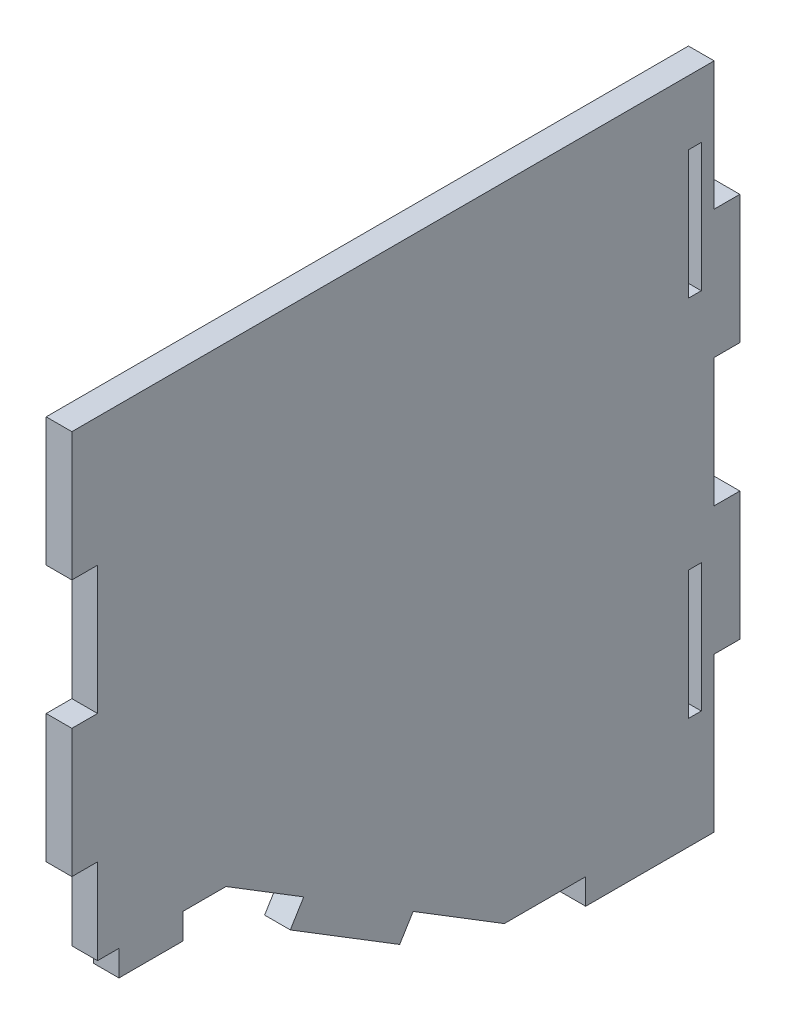
SolidWorks part; units mm, degrees
ref_plane "Front Plane" through (0, 0, 0) normal (0, 0, 1) x (1, 0, 0)
ref_plane "Top Plane" through (0, 0, 0) normal (0, 1, 0) x (1, 0, 0)
ref_plane "Right Plane" through (0, 0, 0) normal (1, 0, 0) x (0, 0, -1)
sketch "Sketch1" plane through (0, 0, 0) normal (0, 1, 0) x (1, 0, 0)
  line L1 (-50, -75) -> (50, -75)
  line L2 (-50, -75) -> (-50, 75)
  line L3 (-50, 75) -> (50, 75)
  line L4 (50, -75) -> (50, 75)
  line L5 (-50, -75) -> (50, 75) construction
  line L6 (-50, 75) -> (50, -75) construction
  point P0 (0, 0)
  dimension "D1" = 100
  dimension "D2" = 150
extrude "Boss-Extrude1" add sketch "Sketch1" along normal blind 150
sketch "Sketch13" plane through (50, 0, 0) normal (1, 0, 0) x (0, 0, -1)
  line L0 (-45, 40) -> (20, 0)
  line L1 (-75, 0) -> (-45, 0)
  line L2 (-75, 0) -> (-75, 40)
  line L3 (-75, 40) -> (-45, 40)
  line L5 (-75, 0) -> (75, 0) construction
  line L8 (-45, 0) -> (20, 0)
  dimension "D1" = 30
  dimension "D2" = 40
  dimension "D3" = 55
extrude "Cut-Extrude7" cut sketch "Sketch13" against normal up to next
shell "Shell1" thickness 5 removed face at (0, 150, 0)
sketch "Sketch3" plane through (0, 0, 0) normal (0, -1, 0) x (1, 0, 0)
  line L1 (50, 45) -> (50, 75) construction
  circle A0 centre (0, 60) radius 4
  circle A1 centre (-5, 50) radius 1.5
  circle A2 centre (5, 50) radius 1.5
  dimension "D3" = 8
  dimension "D4" = 3
  dimension "D5" = 10
  dimension "D7" = 10
  dimension "D8" = 5
  dimension "D1" = 60
  dimension "D2" = 50
extrude "Cut-Extrude2" cut sketch "Sketch3" against normal up to next
sketch "Sketch5" plane through (0, 0, 75) normal (0, 0, 1) x (1, 0, 0)
  line L0 (50, 150) -> (50, 40) construction
  line L1 (-25, 50) -> (25, 50)
  line L2 (-25, 50) -> (-25, 97)
  line L3 (-25, 97) -> (25, 97)
  line L4 (25, 50) -> (25, 97)
  line L5 (-25, 50) -> (25, 97) construction
  line L6 (-25, 97) -> (25, 50) construction
  line L7 (-50, 150) -> (50, 150) construction
  point P0 (0, 73.5)
  dimension "D1" = 50
  dimension "D2" = 47
  dimension "D3" = 50
  dimension "D4" = 76.5
extrude "Boss-Extrude3" add sketch "Sketch5" along normal blind 1
sketch "Sketch8" plane through (0, 0, 75) normal (0, 0, 1) x (1, 0, 0)
  line L0 (-50, 150) -> (-50, 40) construction
  line L1 (-25, 100) -> (25, 100)
  line L2 (-25, 100) -> (-25, 139)
  line L3 (-25, 139) -> (25, 139)
  line L4 (25, 100) -> (25, 139)
  line L5 (-25, 100) -> (25, 139) construction
  line L6 (-25, 139) -> (25, 100) construction
  line L7 (-50, 150) -> (50, 150) construction
  point P0 (0, 119.5)
  dimension "D1" = 50
  dimension "D2" = 39
  dimension "D3" = 50
  dimension "D4" = 50
extrude "Cut-Extrude3" cut sketch "Sketch8" against normal up to next
sketch "Sketch18" plane through (0, 0, 70) normal (0, 0, -1) x (-1, 0, 0)
  line L0 (-25, 139) -> (25, 139) construction
  line L1 (30, 99) -> (-26, 99)
  line L2 (30, 99) -> (30, 140)
  line L3 (30, 140) -> (-26, 140)
  line L4 (-26, 99) -> (-26, 140)
  line L6 (-25, 100) -> (-25, 139) construction
  line L7 (25, 139) -> (25, 100) construction
  dimension "D1" = 1
  dimension "D2" = 41
  dimension "D3" = 1
  dimension "D4" = 5
extrude "Cut-Extrude9" cut sketch "Sketch18" against normal blind 2
sketch "Sketch20" plane through (0, 0, 76) normal (0, 0, 1) x (1, 0, 0)
  line L0 (25, 97) -> (-25, 97) construction
  line L1 (-23, 96) -> (23, 96)
  line L2 (-23, 96) -> (-23, 51)
  line L3 (-23, 51) -> (23, 51)
  line L4 (23, 96) -> (23, 51)
  line L5 (-25, 50) -> (25, 50) construction
  line L6 (25, 50) -> (25, 97) construction
  line L7 (-25, 97) -> (-25, 50) construction
  dimension "D1" = 1
  dimension "D2" = 1
  dimension "D3" = 2
  dimension "D4" = 2
extrude "Cut-Extrude10" cut sketch "Sketch20" against normal blind 15 from offset 4 offset against normal yes
sketch "Sketch21" plane through (0, 45, 0) normal (0, 1, 0) x (1, 0, 0)
  line L1 (9, -52.5) -> (-9, -52.5)
  line L2 (9, -52.5) -> (9, -37.5)
  line L3 (9, -37.5) -> (-9, -37.5)
  line L4 (-9, -52.5) -> (-9, -37.5)
  circle A0 centre (5, -50) radius 1.5 construction
  circle A1 centre (-5, -50) radius 1.5 construction
  dimension "D3" = 4
  dimension "D1" = 4
  dimension "D2" = 2.5
  dimension "D4" = 15
extrude "Cut-Extrude11" cut sketch "Sketch21" against normal blind 2.5
sketch "Sketch22" plane through (-45, 0, 0) normal (1, 0, 0) x (0, 0, -1)
  line L0 (70, 150) -> (-70, 150) construction
  line L5 (70, 150) -> (70, 5) construction
  line L7 (-43.5848, 45) -> (21.4152, 5) construction
  line L8 (10, 150) -> (10, 12.0247)
  line L11 (10, 150) -> (5, 150)
  line L14 (5, 150) -> (5, 15.1017)
  line L15 (5, 15.1017) -> (10, 12.0247)
  dimension "D1" = 60
  dimension "D3" = 5
extrude "Boss-Extrude6" add sketch "Sketch22" along normal blind 5
mirror "Mirror2" about plane through (0, 0, 0) normal (1, 0, 0) of "Boss-Extrude6"
sketch "Sketch23" plane through (-45, 0, 0) normal (1, 0, 0) x (0, 0, -1)
  line L0 (16, 150) -> (21, 150)
  line L1 (70, 150) -> (10, 150) construction
  line L3 (21, 150) -> (21, 5.2555)
  line L4 (21, 5.2555) -> (16, 8.3324)
  line L6 (10, 12.0247) -> (10, 150) construction
  line L7 (16, 150) -> (16, 8.3324)
  line L8 (10, 12.0247) -> (21.4152, 5) construction
  dimension "D1" = 6
  dimension "D2" = 5
extrude "Boss-Extrude7" add sketch "Sketch23" along normal up to next
sketch "Sketch36" plane through (50, 0, 0) normal (1, 0, 0) x (0, 0, -1)
  line L0 (-75, 150) -> (75, 150)
  line L1 (75, 150) -> (75, 0)
  line L2 (75, 0) -> (20, 0)
  line L3 (20, 0) -> (75, 0) construction
  line L4 (20, 0) -> (-45, 40)
  line L5 (-45, 40) -> (-75, 40)
  line L6 (-75, 40) -> (-75, 150)
extrude "Boss-Extrude8" add sketch "Sketch36" along normal blind 1
sketch "Sketch24" plane through (-45, 0, 0) normal (1, 0, 0) x (0, 0, -1)
  line L1 (66, 135) -> (63, 135)
  line L2 (66, 135) -> (66, 105)
  line L3 (66, 105) -> (63, 105)
  line L4 (63, 135) -> (63, 105)
  line L5 (70, 150) -> (21, 150) construction
  line L6 (70, 5) -> (21.4152, 5) construction
  line L7 (66, 20) -> (63, 20)
  line L8 (66, 20) -> (66, 50)
  line L9 (66, 50) -> (63, 50)
  line L10 (63, 20) -> (63, 50)
  line L11 (75, 150) -> (75, 0) construction
  dimension "D1" = 15
  dimension "D2" = 30
  dimension "D3" = 3
  dimension "D4" = 15
  dimension "D5" = 9
extrude "Cut-Extrude12" cut sketch "Sketch24" against normal through all both and the other way through all
sketch "Sketch28" plane through (0, 0, 76) normal (0, 0, 1) x (1, 0, 0)
  line L0 (-25, 73.5) -> (25, 73.5) construction
  line L1 (-25, 97) -> (-25, 50) construction
  line L2 (25, 50) -> (25, 97) construction
  line L3 (-25, 77.511) -> (25, 77.511) construction
  text T0 "SCAN\r\nHERE" font "Impact" height 10
extrude "Cut-Extrude14" cut sketch "Sketch28" against normal blind 1
sketch "Sketch30" plane through (0, 0, -75) normal (0, 0, -1) x (-1, 0, 0)
  text T0 "IBE VAN DE VEIRE\r\nSTEF GIELEN" font "Comic Sans MS" height 5
extrude "Cut-Extrude16" cut sketch "Sketch30" against normal blind 1
sketch "Sketch33" plane through (0, 150, 0) normal (0, 1, 0) x (1, 0, 0)
  line L1 (-45, 5) -> (45, 5)
  line L2 (-45, 5) -> (-45, 21)
  line L3 (-45, 21) -> (45, 21)
  line L4 (45, 5) -> (45, 21)
extrude "Cut-Extrude18" cut sketch "Sketch33" against normal blind 40
sketch "Sketch35" plane through (0, 150, 0) normal (0, 1, 0) x (1, 0, 0)
  line L0 (51, 75) -> (-50, 75) construction
  line L1 (45, 75) -> (-50, 75)
  line L2 (45, 75) -> (45, -153.7649)
  line L3 (45, -153.7649) -> (-50, -153.7649)
  line L4 (-50, 75) -> (-50, -153.7649)
  dimension "D1" = 228.7649
extrude "Cut-Extrude19" cut sketch "Sketch35" against normal through all
sketch "Sketch39" plane through (0, 0, 75) normal (0, 0, 1) x (1, 0, 0)
  line L0 (51, 150) -> (51, 40) construction
  line L1 (45, 150) -> (51, 150)
  line L2 (45, 150) -> (45, 120)
  line L3 (45, 120) -> (51, 120)
  line L4 (51, 150) -> (51, 120)
  line L5 (45, 120) -> (51, 120) construction
extrude "Boss-Extrude9" add sketch "Sketch39" along normal blind 6
pattern_linear "LPattern1" count 2 spacing 60 along (0, -1, 0) of "Boss-Extrude9"
ref_plane "Plane1" through (0, 0, 0) normal (1, 0, 0) x (0, 0, -1)
sketch "Sketch41" plane through (51, 0, 0) normal (1, 0, 0) x (0, 0, -1)
  line L1 (75, 150) -> (69, 150)
  line L2 (75, 150) -> (75, 120)
  line L3 (75, 120) -> (69, 120)
  line L4 (69, 150) -> (69, 120)
  dimension "D1" = 6
  dimension "D2" = 30
extrude "Cut-Extrude20" cut sketch "Sketch41" against normal blind 6
pattern_linear "LPattern2" count 3 spacing 60 along (0, -1, 0) of "Cut-Extrude20"
sketch "Sketch42" plane through (0, 0, 0) normal (0, -1, 0) x (1, 0, 0)
  line L0 (45, -20) -> (45, -69) construction
  line L1 (51, -69) -> (45, -69)
  line L2 (51, -69) -> (51, -39)
  line L3 (51, -39) -> (45, -39)
  line L4 (45, -69) -> (45, -39)
  dimension "D1" = 30
extrude "Boss-Extrude10" add sketch "Sketch42" along normal blind 6
sketch "Sketch43" plane through (0, 8.927, -5.4936) normal (0, -0.8517, 0.5241) x (1, 0, 0)
  line L0 (45, 59.2885) -> (45, -17.0332) construction
  line L1 (45, 37.9668) -> (51, 37.9668)
  line L2 (45, 37.9668) -> (45, 7.9668)
  line L3 (45, 7.9668) -> (51, 7.9668)
  line L4 (51, 37.9668) -> (51, 7.9668)
  line L5 (51, 59.2885) -> (51, -17.0332) construction
  line L6 (45, -17.0332) -> (51, -17.0332) construction
  dimension "D1" = 30
  dimension "D2" = 25
extrude "Boss-Extrude11" add sketch "Sketch43" along normal blind 6
sketch "Sketch44" plane through (0, 40, 0) normal (0, -1, 0) x (1, 0, 0)
  line L0 (51, 75) -> (51, 45) construction
  line L1 (51, 70) -> (45, 70)
  line L2 (51, 70) -> (51, 55)
  line L3 (51, 55) -> (45, 55)
  line L4 (45, 70) -> (45, 55)
  line L5 (45, 75) -> (45, 45) construction
  line L6 (45, 75) -> (51, 75) construction
  dimension "D1" = 15
  dimension "D2" = 5
extrude "Boss-Extrude12" add sketch "Sketch44" along normal blind 6
